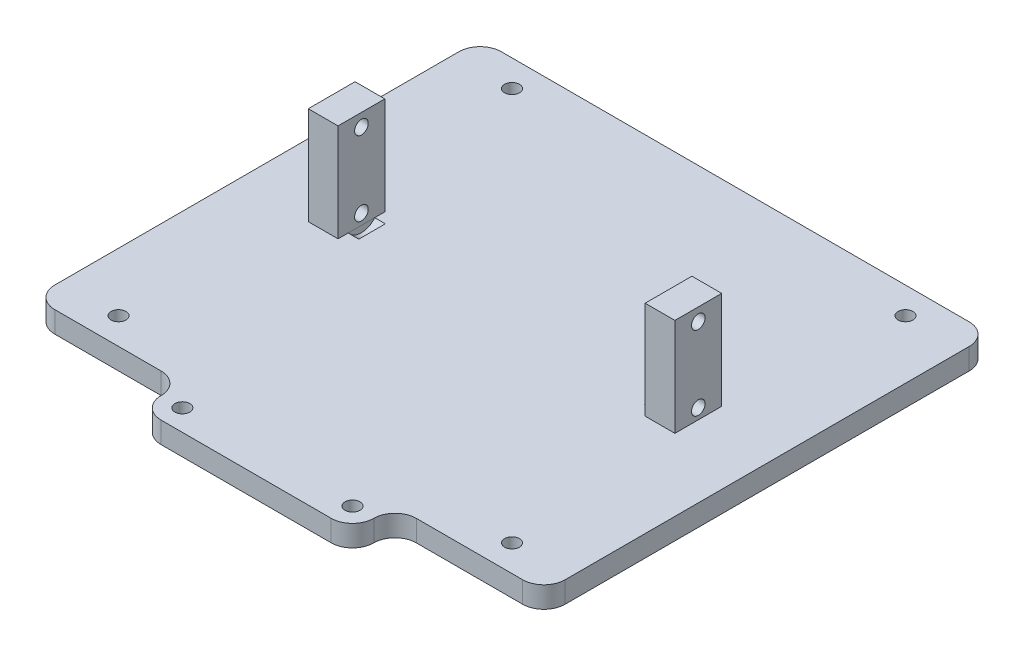
SolidWorks part; units mm, degrees
ref_plane "정면" through (0, 0, 0) normal (0, 0, 1) x (1, 0, 0)
ref_plane "윗면" through (0, 0, 0) normal (0, 1, 0) x (1, 0, 0)
ref_plane "우측면" through (0, 0, 0) normal (1, 0, 0) x (0, 0, -1)
sketch "스케치1" plane through (0, 0, 0) normal (0, 1, 0) x (1, 0, 0)
  line L0 (-25, -52.5) -> (-60, -52.5)
  line L1 (60, 52.5) -> (-60, 52.5)
  line L2 (60, 52.5) -> (60, -52.5)
  line L3 (60, -52.5) -> (25, -52.5)
  line L4 (-60, 52.5) -> (-60, -52.5)
  line L5 (60, 52.5) -> (-60, -52.5) construction
  line L6 (60, -52.5) -> (-60, 52.5) construction
  line L7 (25, -62.5) -> (-25, -62.5)
  line L8 (25, -62.5) -> (25, -52.5)
  line L10 (-25, -62.5) -> (-25, -52.5)
  line L11 (25, -62.5) -> (-25, -52.5) construction
  line L12 (25, -52.5) -> (-25, -62.5) construction
  point P0 (0, 0)
  point P6 (0, -57.5)
  dimension "D1" = 120
  dimension "D2" = 105
  dimension "D3" = 50
  dimension "D4" = 10
extrude "보스-돌출1" add sketch "스케치1" along normal blind 5
fillet "필렛1" radius 5 8 edges at (60, 2.5, -52.5) (60, 2.5, 52.5) (-60, 2.5, -52.5) (-60, 2.5, 52.5) (-25, 2.5, 52.5) (25, 2.5, 52.5) (25, 2.5, 62.5) (-25, 2.5, 62.5)
sketch "스케치2" plane through (0, 5, 0) normal (0, 1, 0) x (1, 0, 0)
  line L0 (-43.1, 29.5) -> (-43.1, -5.3) construction
  line L1 (-36.1, -4.8) -> (-43.1, -4.8)
  line L2 (-36.1, -4.8) -> (-36.1, 6.2)
  line L3 (-36.1, 6.2) -> (-43.1, 6.2)
  line L4 (-43.1, -4.8) -> (-43.1, 6.2)
  line L5 (-61.9, -0.8) -> (-43.1, -0.8) construction
  line L6 (-43.1, 2.2) -> (-61.9, 2.2) construction
  dimension "D1" = 7
  dimension "D2" = 4
  dimension "D3" = 4
extrude "보스-돌출2" add sketch "스케치2" along normal blind 23 separate body
sketch "스케치3" plane through (-36.1, 0, 0) normal (1, 0, 0) x (0, 0, -1)
  circle A0 centre (0.7, 7.5) radius 1.5 construction
  circle A1 centre (0.7, 25) radius 1.5 construction
  circle A2 centre (0.7, 25) radius 1.6
  circle A3 centre (0.7, 7.5) radius 1.6
  circle A4 centre (0.7, 7.5) radius 1.5 construction
  circle A5 centre (0.7, 25) radius 1.5 construction
  dimension "D1" = 3.2
  dimension "D2" = 3.2
extrude "컷-돌출1" cut sketch "스케치3" against normal through all
mirror "대칭 복사1" about plane through (0, 0, 0) normal (1, 0, 0) of bodies 103
sketch "스케치5" plane through (0, 5, 0) normal (0, 1, 0) x (1, 0, 0)
  circle A0 centre (-46.25, -46.25) radius 1.75 construction
  circle A1 centre (-46.25, 46.25) radius 1.75 construction
  circle A2 centre (46.25, 46.25) radius 1.75 construction
  circle A3 centre (46.25, -46.25) radius 1.75 construction
  circle A4 centre (-46.25, -46.25) radius 1.75
  circle A5 centre (-46.25, 46.25) radius 1.75
  circle A6 centre (46.25, 46.25) radius 1.75
  circle A7 centre (46.25, -46.25) radius 1.75
extrude "컷-돌출3" cut sketch "스케치5" against normal through all
sketch "스케치6" plane through (0, 5, 0) normal (0, 1, 0) x (1, 0, 0)
  circle A0 centre (20, -57.5) radius 1.75 construction
  circle A1 centre (-20, -57.5) radius 1.75 construction
  circle A2 centre (20, -57.5) radius 1.75
  circle A3 centre (-20, -57.5) radius 1.75
extrude "컷-돌출4" cut sketch "스케치6" against normal through all
sketch "Sketch2" plane through (36.1, 0, 0) normal (-1, 0, 0) x (0, 0, 1)
  circle A0 centre (-0.7, 7.5) radius 4
  point P3 (-0.7, 7.5)
  dimension "D1" = 8
extrude "Cut-Extrude1" cut sketch "Sketch2" along normal blind 2.5
sketch "Sketch3" plane through (-36.1, 0, 0) normal (1, 0, 0) x (0, 0, -1)
  circle A0 centre (0.7, 7.5) radius 4
  point P3 (0.7, 7.5)
  dimension "D1" = 8
extrude "Cut-Extrude2" cut sketch "Sketch3" along normal blind 2.5
